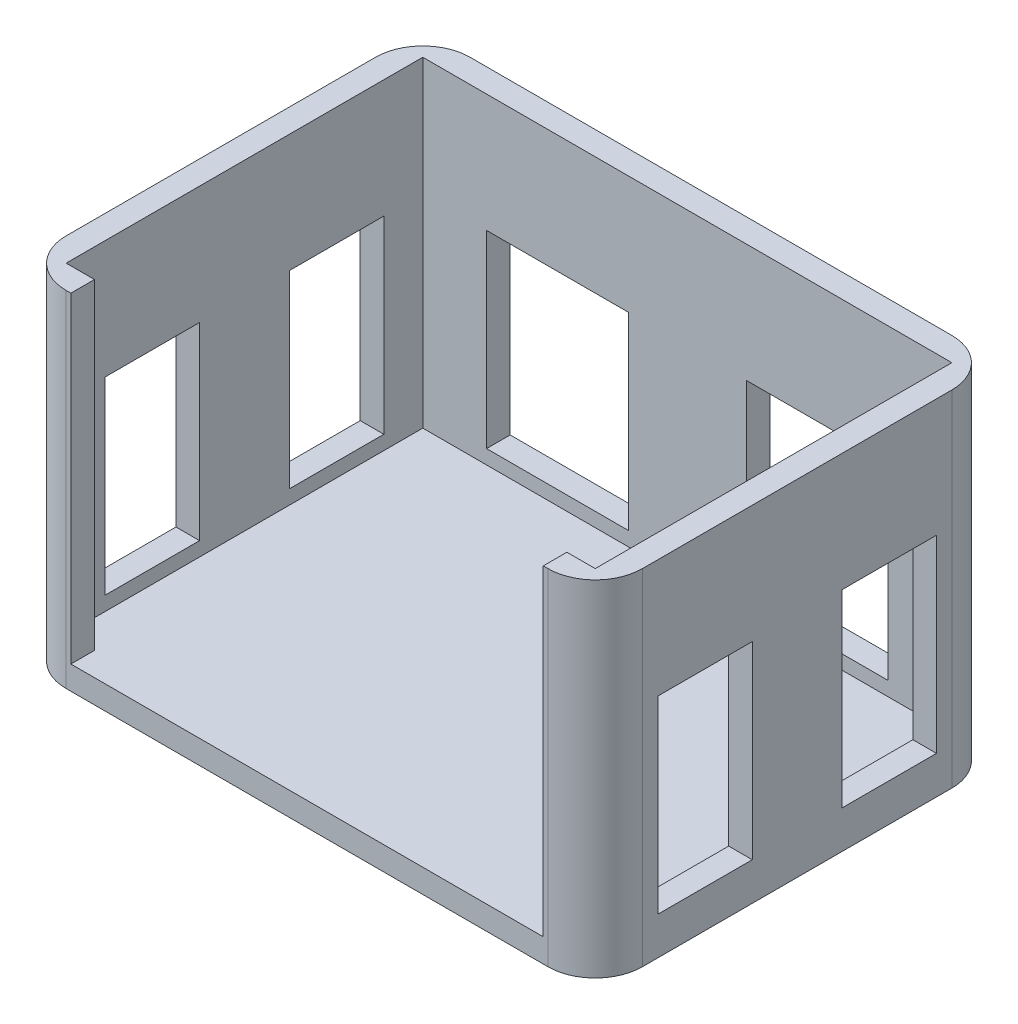
SolidWorks part; units mm, degrees
ref_plane "Front Plane" through (0, 0, 0) normal (0, 0, 1) x (1, 0, 0)
ref_plane "Top Plane" through (0, 0, 0) normal (0, 1, 0) x (1, 0, 0)
ref_plane "Right Plane" through (0, 0, 0) normal (1, 0, 0) x (0, 0, -1)
sketch "Sketch1" plane through (0, 0, 0) normal (0, 1, 0) x (1, 0, 0)
  line L1 (0, 0) -> (122, 0)
  line L2 (0, 0) -> (0, 85.5)
  line L3 (0, 85.5) -> (122, 85.5)
  line L4 (122, 0) -> (122, 85.5)
  dimension "D1" = 122
  dimension "D2" = 85.5
extrude "Boss-Extrude1" add sketch "Sketch1" along normal blind 5
sketch "Sketch2" plane through (0, 5, 0) normal (0, 1, 0) x (1, 0, 0)
  line L0 (0, 85.5) -> (0, 0) construction
  line L1 (5, 5) -> (11, 5)
  line L2 (5, 5) -> (5, 80.5)
  line L3 (5, 80.5) -> (117, 80.5)
  line L4 (117, 5) -> (117, 80.5)
  line L5 (122, 0) -> (122, 85.5) construction
  line L6 (122, 85.5) -> (0, 85.5) construction
  line L7 (0, 0) -> (122, 0) construction
  line L8 (11, 5) -> (11, 0)
  line L9 (0, 0) -> (11, 0)
  line L10 (0, 0) -> (0, 85.5)
  line L11 (0, 85.5) -> (122, 85.5)
  line L12 (122, 0) -> (122, 85.5)
  line L13 (111, 5) -> (111, 0)
  line L14 (111, 0) -> (122, 0)
  line L15 (111, 5) -> (117, 5)
  line L16 (0, 0) -> (11, -25.5191) construction
  line L17 (11, -25.5191) -> (11, 0) construction
  line L18 (122, 0) -> (111, -25.5191) construction
  line L19 (111, -25.5191) -> (111, 0) construction
  dimension "D1" = 5
  dimension "D2" = 5
  dimension "D3" = 5
  dimension "D4" = 5
  dimension "D5" = 100
extrude "Boss-Extrude2" add sketch "Sketch2" along normal blind 68
sketch "Sketch3" plane through (122, 0, 0) normal (1, 0, 0) x (0, 0, -1)
  line L0 (0, 28) -> (13.25, 28) construction
  line L1 (13.25, 48) -> (33.25, 48)
  line L2 (13.25, 48) -> (13.25, 8)
  line L3 (13.25, 8) -> (33.25, 8)
  line L4 (33.25, 48) -> (33.25, 8)
  line L5 (52.25, 48) -> (72.25, 48)
  line L6 (52.25, 48) -> (52.25, 8)
  line L7 (52.25, 8) -> (72.25, 8)
  line L8 (72.25, 48) -> (72.25, 8)
  line L9 (0, 73) -> (0, 0) construction
  line L10 (72.25, 28) -> (85.5, 28) construction
  line L11 (85.5, 73) -> (85.5, 0) construction
  line L12 (23.25, 48) -> (23.25, 73) construction
  line L13 (0, 73) -> (85.5, 73) construction
  point P20 (32.3087, 11.5403)
  dimension "D1" = 25
  dimension "D2" = 40
  dimension "D3" = 19
  dimension "D4" = 20
extrude "Cut-Extrude1" cut sketch "Sketch3" against normal through all and the other way through all
sketch "Sketch4" plane through (0, 0, -85.5) normal (0, 0, -1) x (-1, 0, 0)
  line L0 (-96.1035, 73) -> (-96.1035, 48) construction
  line L1 (-103.5, 48) -> (-73.5, 48)
  line L2 (-103.5, 48) -> (-103.5, 8)
  line L3 (-103.5, 8) -> (-73.5, 8)
  line L4 (-73.5, 48) -> (-73.5, 8)
  line L5 (-48.5, 48) -> (-18.5, 48)
  line L6 (-48.5, 48) -> (-48.5, 8)
  line L7 (-48.5, 8) -> (-18.5, 8)
  line L8 (-18.5, 48) -> (-18.5, 8)
  line L9 (-122, 73) -> (0, 73) construction
  line L10 (-122, 36.5) -> (-103.5, 36.5) construction
  line L11 (-122, 73) -> (-122, 0) construction
  line L12 (-18.5, 36.5) -> (0, 36.5) construction
  line L13 (0, 73) -> (0, 0) construction
  dimension "D1" = 25
  dimension "D2" = 40
  dimension "D3" = 25
  dimension "D4" = 30
extrude "Cut-Extrude2" cut sketch "Sketch4" against normal up to next
fillet "Fillet1" radius 10 4 edges at (122, 36.5, 0) (122, 36.5, -85.5) (0, 36.5, -85.5) (0, 36.5, 0)
